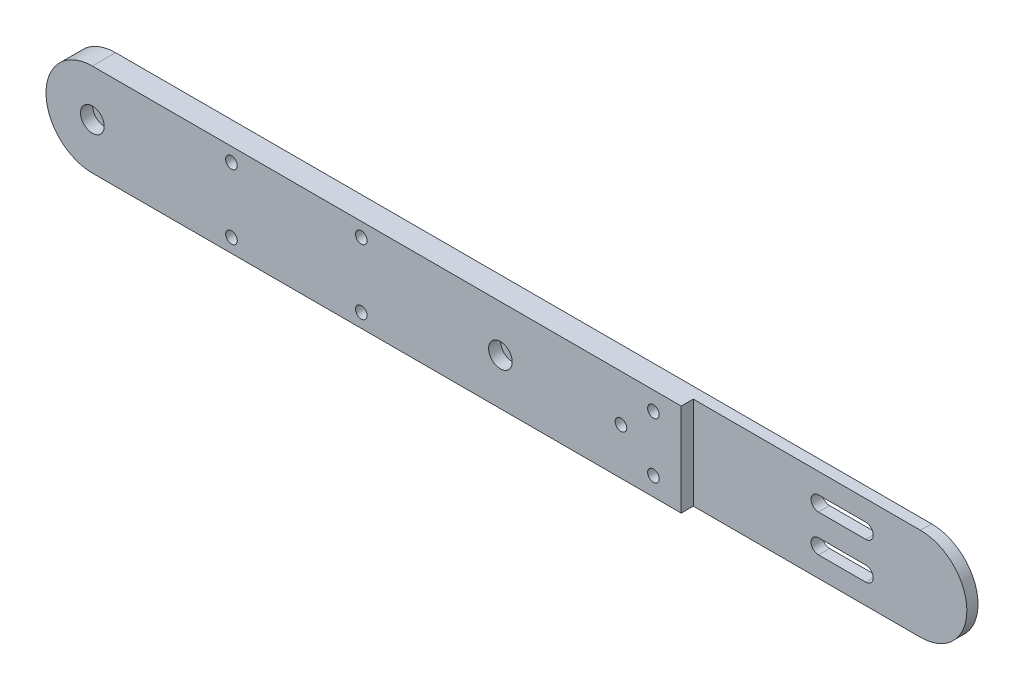
SolidWorks part; units mm, degrees
ref_plane "前视基准面" through (0, 0, 0) normal (0, 0, 1) x (1, 0, 0)
ref_plane "上视基准面" through (0, 0, 0) normal (0, 1, 0) x (1, 0, 0)
ref_plane "右视基准面" through (0, 0, 0) normal (1, 0, 0) x (0, 0, -1)
other "Configuration Table"
sketch "草图1" plane through (0, 0, 0) normal (0, 0, 1) x (1, 0, 0)
  line L0 (0, 0) -> (176, 0) construction
  line L5 (0, 10) -> (176, 10)
  line L6 (0, 10) -> (0, -10)
  line L7 (0, -10) -> (176, -10)
  line L8 (176, 10) -> (176, -10)
  circle A2 centre (0, 0) radius 10
  circle A5 centre (88, 0) radius 2.55
  circle A8 centre (88, 0) radius 1.1
  circle A9 centre (0, 0) radius 2.55
  circle A10 centre (0, 0) radius 1.1
  circle A11 centre (176, 0) radius 10
  dimension "D1" = 20
  dimension "D2" = 176
  dimension "D4" = 2.2
  dimension "D5" = 5.1
  dimension "D3" = 176
extrude "凸台-拉伸1" add sketch "草图1" along normal blind 5 contours A2 | L7 L8 L5 L6 | A11
extrude "切除-拉伸2" cut sketch "草图1<3>" along normal through all contours A10 | A8
sketch "草图1<3>" plane through (0, 0, 0) normal (0, 0, 1) x (1, 0, 0) same geometry as "草图1"
extrude "切除-拉伸3" cut sketch "草图1<4>" along normal blind 2.6 contours A5 | A9
sketch "草图1<4>" plane through (0, 0, 0) normal (0, 0, 1) x (1, 0, 0) same geometry as "草图1"
sketch "草图2" plane through (0, 0, 0) normal (0, 0, -1) x (-1, 0, 0)
  line L0 (0, -10) -> (-176, -10) construction
  line L1 (0, 10) -> (-176, 10) construction
  line L2 (-121, 6) -> (-121, -6) construction
  circle A0 centre (-121, -6) radius 1.25
  circle A1 centre (-121, 6) radius 1.25
  circle A2 centre (-121, -6) radius 2
  circle A3 centre (-121, 6) radius 2
  circle A4 centre (-88, 0) radius 1.1 construction
  circle A5 centre (-114, 0) radius 2
  circle A6 centre (-114, 0) radius 1.25
  circle A7 centre (-58, 7) radius 1.25
  circle A9 centre (-58, 7) radius 2
  circle A10 centre (-30, 7) radius 2
  circle A11 centre (-30, 7) radius 1.25
  circle A12 centre (-58, -7) radius 2
  circle A13 centre (-58, -7) radius 1.25
  circle A14 centre (-30, -7) radius 1.25
  circle A15 centre (-30, -7) radius 2
  point P16 (-121, 0)
  dimension "D1" = 4
  dimension "D2" = 2.5
  dimension "D3" = 33
  dimension "D4" = 4
  dimension "D5" = 4
  dimension "D6" = 7
  dimension "D7" = 30
  dimension "D8" = 30
  dimension "D9" = 3
  dimension "D10" = 3
extrude "切除-拉伸4" cut sketch "草图2" against normal through all contours A1 | A0 | A6 | A13 | A14 | A11 | A7
extrude "切除-拉伸5" cut sketch "草图2<3>" along normal offset from surface (2.5 mm away) 2.5 from surface contours A3 | A2 | A5 | A9 | A10 | A15 | A12 up to face at (56.75, 7, 0) starting at face at (56.75, 7, 5)
sketch "草图2<3>" plane through (0, 0, 0) normal (0, 0, -1) x (-1, 0, 0) same geometry as "草图2"
sketch "草图3" plane through (0, 10, 0) normal (0, 1, 0) x (1, 0, 0)
  line L0 (0, 0) -> (176, 0) construction
  line L1 (127, 0) -> (186, 0)
  line L2 (127, 0) -> (127, -2.6)
  line L3 (127, -2.6) -> (186, -2.6)
  line L4 (186, 0) -> (186, -2.6)
  dimension "D1" = 59
  dimension "D2" = 2.6
extrude "切除-拉伸6" cut sketch "草图3" against normal through all
sketch "草图4" plane through (0, 0, 5) normal (0, 0, 1) x (1, 0, 0)
  line L0 (164.2, -2.4) -> (154, -2.4)
  line L5 (164.2, -2.4) -> (164.2, -5.6)
  line L6 (164.2, -5.6) -> (154, -5.6)
  line L7 (154, -2.4) -> (154, -5.6)
  line L8 (164.2, 5.6) -> (154, 5.6)
  line L9 (164.2, 5.6) -> (164.2, 2.4)
  line L10 (164.2, 2.4) -> (154, 2.4)
  line L11 (154, 5.6) -> (154, 2.4)
  line L12 (154, 4) -> (154, -4)
  line L13 (186, 0) -> (154, 0)
  circle A3 centre (164.2, -4) radius 1.6
  circle A4 centre (154, -4) radius 1.6
  circle A5 centre (164.2, 4) radius 1.6
  circle A6 centre (154, 4) radius 1.6
  arc A7 (176, -10) -> (176, 10) centre (176, 0) ccw construction
  dimension "D1" = 10.2
  dimension "D3" = 3.2
  dimension "D4" = 3.2
  dimension "D2" = 8
  dimension "D5" = 32
extrude "切除-拉伸7" cut sketch "草图4" against normal through all contours A6 | L10 L11 L8 L9 | A5 | L6 L7 L0 L5 | A4 | A3
ref_plane "基准面1" through (0, 0, 15) normal (0, 0, 1) x (1, 0, 0)
mirror "镜向2" about plane through (0, 0, 15) normal (0, 0, 1) of bodies 153
sketch "草图5" plane through (0, 0, 15) normal (0, 0, 1) x (1, 0, 0)
  line L1 (-53.9325, 56.6387) -> (222.9926, 56.6387)
  line L2 (-53.9325, 56.6387) -> (-53.9325, -68.056)
  line L3 (-53.9325, -68.056) -> (222.9926, -68.056)
  line L4 (222.9926, 56.6387) -> (222.9926, -68.056)
extrude "切除-拉伸8" cut sketch "草图5" against normal through all
